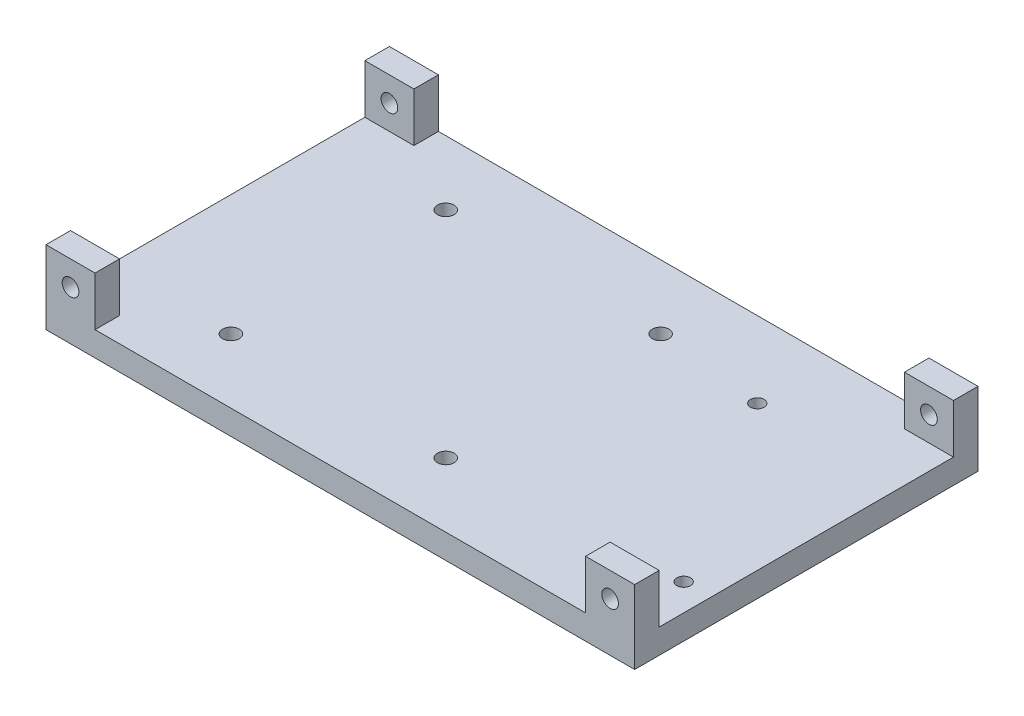
SolidWorks part; units mm, degrees
ref_plane "Front Plane" through (0, 0, 0) normal (0, 0, 1) x (1, 0, 0)
ref_plane "Top Plane" through (0, 0, 0) normal (0, 1, 0) x (1, 0, 0)
ref_plane "Right Plane" through (0, 0, 0) normal (1, 0, 0) x (0, 0, -1)
sketch "Sketch1" plane through (0, 0, 0) normal (0, 1, 0) x (1, 0, 0)
  line L1 (0, 0) -> (-120, 0)
  line L2 (0, 0) -> (0, 70)
  line L3 (0, 70) -> (-120, 70)
  line L4 (-120, 0) -> (-120, 70)
  dimension "D1" = 120
  dimension "D2" = 70
extrude "Boss-Extrude2" add sketch "Sketch1" along normal blind 5
sketch "Sketch2" plane through (0, 5, 0) normal (0, 1, 0) x (1, 0, 0)
  line L1 (-120, 0) -> (-110, 0)
  line L2 (-120, 0) -> (-120, 5)
  line L3 (-120, 5) -> (-110, 5)
  line L4 (-110, 0) -> (-110, 5)
  line L5 (-120, 70) -> (-110, 70)
  line L6 (-120, 70) -> (-120, 65)
  line L7 (-120, 65) -> (-110, 65)
  line L8 (-110, 70) -> (-110, 65)
  line L9 (0, 0) -> (-10, 0)
  line L10 (0, 0) -> (0, 5)
  line L11 (0, 5) -> (-10, 5)
  line L12 (-10, 0) -> (-10, 5)
  line L13 (0, 70) -> (-10, 70)
  line L14 (0, 70) -> (0, 65)
  line L15 (0, 65) -> (-10, 65)
  line L16 (-10, 70) -> (-10, 65)
  dimension "D1" = 5
  dimension "D2" = 10
extrude "Boss-Extrude3" add sketch "Sketch2" along normal blind 10
hole_wizard "M3 Clearance Hole1" positions "Sketch4" profile "Sketch3" hole size "M3" standard "ANSI Metric" end condition through all
sketch "Sketch4" plane through (0, 0, 0) normal (0, 0, 1) x (1, 0, 0)
  line L0 (-120, 15) -> (-120, 0) construction
  line L1 (-120, 15) -> (-110, 15) construction
  line L2 (0, 15) -> (0, 0) construction
  point P0 (-115, 10)
  point P2 (-5, 10)
  dimension "D1" = 5
  dimension "D2" = 5
  dimension "D3" = 5
sketch "Sketch3" plane through (-115, 10, 0) normal (1, 0, 0) x (0, -1, 0)
  line L0 (0, 0) -> (0, 70)
  line L1 (0, 70) -> (1.7, 70)
  line L2 (1.7, 70) -> (1.7, 0)
  line L5 (1.7, 0) -> (0, 0)
  line L11 (0, -6.35) -> (0, 107.95) construction
  dimension "Thru Hole Dia." = 3.4
  dimension "Thru Hole Depth" = 70
sketch "Sketch5" plane through (0, 0, 0) normal (0, -1, 0) x (1, 0, 0)
  circle A0 centre (-29.5, -54.5) radius 1.39
  circle A1 centre (-5.5, -15.5) radius 1.39
  circle A2 centre (-29.5, -54.5) radius 1.39 construction
  circle A3 centre (-5.5, -15.5) radius 1.39 construction
extrude "Cut-Extrude1" cut sketch "Sketch5" against normal through all
hole_wizard "M3 Clearance Hole2" positions "Sketch7" profile "Sketch8" hole size "M3" standard "ANSI Metric" end condition through all
sketch "Sketch7" plane through (0, 0, 0) normal (0, -1, 0) x (-1, 0, 0)
  circle A0 centre (95.4, 56.9) radius 1.75 construction
  circle A1 centre (95.4, 13.1) radius 1.75 construction
  circle A2 centre (51.6, 13.1) radius 1.75 construction
  circle A3 centre (51.6, 56.9) radius 1.75 construction
  point P0 (95.4, 13.1)
  point P2 (51.6, 13.1)
  point P4 (51.6, 56.9)
  point P6 (95.4, 56.9)
sketch "Sketch8" plane through (-95.4, 0, -13.1) normal (1, 0, 0) x (0, 0, -1)
  line L0 (0, 0) -> (0, 15)
  line L1 (0, 15) -> (1.7, 15)
  line L2 (1.7, 15) -> (1.7, 0)
  line L5 (1.7, 0) -> (0, 0)
  line L11 (0, -6.35) -> (0, 107.95) construction
  dimension "Thru Hole Dia." = 3.4
  dimension "Thru Hole Depth" = 15
